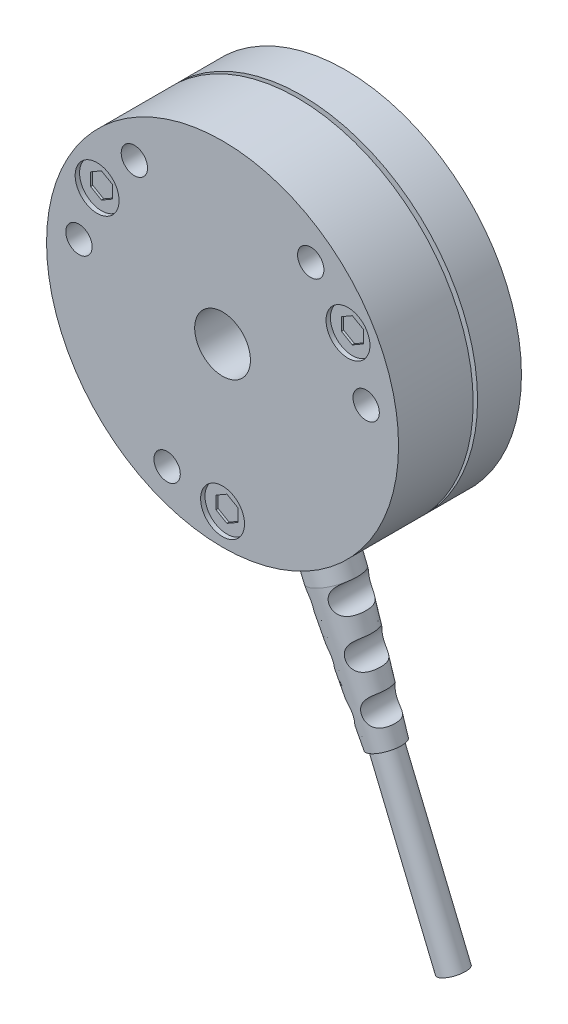
SolidWorks part; units mm, degrees
other "Camera1"
material "Plain Carbon Steel"
ref_plane "Front Plane" through (0, 0, 0) normal (0, 0, 1) x (1, 0, 0)
ref_plane "Top Plane" through (0, 0, 0) normal (0, 1, 0) x (1, 0, 0)
ref_plane "Right Plane" through (0, 0, 0) normal (1, 0, 0) x (0, 0, -1)
sketch "Sketch1" plane through (0, 0, 0) normal (0, 0, 1) x (1, 0, 0)
  circle A0 centre (0, 0) radius 20.05
  dimension "D1" = 40.1
extrude "Boss-Extrude1" add sketch "Sketch1" along normal blind 5
sketch "Sketch2" plane through (0, 0, 5) normal (0, 0, 1) x (1, 0, 0)
  circle A0 centre (0, 0) radius 18.5
  dimension "D1" = 37
extrude "Boss-Extrude2" add sketch "Sketch2" along normal blind 0.5
sketch "Sketch3" plane through (0, 0, 5.5) normal (0, 0, 1) x (1, 0, 0)
  circle A0 centre (0, 0) radius 20.05
extrude "Boss-Extrude3" add sketch "Sketch3" along normal blind 8.5
sketch "Sketch7" plane through (0, 0, 14) normal (0, 0, 1) x (1, 0, 0)
  line L0 (0, 0) -> (7.6728, -18.5238) construction
  line L1 (0, 20.05) -> (0, -20.05) construction
  line L2 (-18.5238, -7.6728) -> (18.5238, 7.6728)
  circle A0 centre (0, 0) radius 20.05 construction
  dimension "D1" = 22.5
sketch "Sketch8" plane through (0, 0, 0) normal (0, 0, -1) x (-1, 0, 0)
  line L0 (-18.5238, 7.6728) -> (18.5238, -7.6728)
ref_plane "Plane4" through (0, 0, 0) normal (-0.3827, 0.9239, 0) x (0.9239, 0.3827, 0)
sketch "Sketch4" plane through (0, 0, 0) normal (-0.3827, 0.9239, 0) x (0.9239, 0.3827, 0)
  line L0 (0, 0) -> (0, -14) construction
  line L1 (-20.05, -14) -> (20.05, -14) construction
  line L2 (-20.05, -7) -> (20.05, -7) construction
  line L3 (-20.05, -5.5) -> (-20.05, -14) construction
  line L4 (20.05, -14) -> (20.05, -5.5) construction
  circle A0 centre (0, -9.65) radius 2.65
  dimension "D1" = 5.3
  dimension "D2" = 7
extrude "Boss-Extrude4" add sketch "Sketch4" against normal blind 37.35 contours A0
chamfer "Chamfer1" distance 15 angle 3 1 edges at (11.8449, -35.521, 9.65) first distance on face at (11.8449, -35.521, 9.65)
sketch "Sketch5" plane through (14.2932, -34.5069, 0) normal (0.3827, -0.9239, 0) x (-0.9239, -0.3827, 0)
  circle A0 centre (0, -9.65) radius 1.5
  dimension "D1" = 3
extrude "Boss-Extrude5" add sketch "Sketch5" along normal blind 20
sketch "Sketch6" plane through (0, 0, 0) normal (0, 0, 1) x (1, 0, 0)
  line L0 (11.0013, -19.6346) -> (16.0152, -33.7936) construction
  line L1 (16.0152, -33.7936) -> (18.3361, -40.3477) construction
  line L2 (23.3327, -52.4105) -> (15.679, -33.9329) construction
  line L3 (6.1047, -21.6628) -> (12.5712, -35.2202) construction
  line L4 (12.5712, -35.2202) -> (15.5645, -41.4957) construction
  line L5 (12.9074, -35.0809) -> (20.5611, -53.5585) construction
  line L6 (-921.5262, -418.3454) -> (45272.4504, 18715.8262) construction
  line L7 (-922.1361, -413.1861) -> (45271.8405, 18720.9855) construction
  line L8 (6.1047, -21.6628) -> (11.0013, -19.6346) construction
  circle A0 centre (11.502, -21.0486) radius 1.5
  circle A1 centre (13.1733, -25.7682) radius 1.5
  circle A2 centre (14.8446, -30.4879) radius 1.5
  circle A3 centre (11.0615, -32.0549) radius 1.5
  circle A4 centre (8.906, -27.5358) radius 1.5
  circle A5 centre (6.7505, -23.0167) radius 1.5
  dimension "D1" = 3
  dimension "D2" = 5
  dimension "D3" = 5
extrude "Cut-Extrude1" cut sketch "Sketch6" along normal through all
sketch "Sketch9" plane through (0, 0, 14) normal (0, 0, 1) x (1, 0, 0)
  circle A0 centre (0, 0) radius 16.5 construction
  circle A1 centre (0, -16.5) radius 2.5
  circle A2 centre (-14.2894, 8.25) radius 2.5
  circle A3 centre (14.2894, 8.25) radius 2.5
  dimension "D1" = 33
  dimension "D2" = 5
  dimension "D3" = 3
extrude "Cut-Extrude2" cut sketch "Sketch9" against normal blind 0.5
sketch "Sketch10" plane through (0, 0, 13.5) normal (0, 0, 1) x (1, 0, 0)
  line L0 (-15.5394, 8.9717) -> (-15.5394, 7.5283)
  line L1 (0, -17.9434) -> (1.25, -17.2217)
  line L2 (1.25, -17.2217) -> (1.25, -15.7783)
  line L3 (1.25, -15.7783) -> (0, -15.0566)
  line L4 (0, -15.0566) -> (-1.25, -15.7783)
  line L5 (-1.25, -15.7783) -> (-1.25, -17.2217)
  line L6 (-1.25, -17.2217) -> (0, -17.9434)
  line L7 (-15.5394, 7.5283) -> (-14.2894, 6.8066)
  line L8 (-14.2894, 6.8066) -> (-13.0394, 7.5283)
  line L9 (-13.0394, 7.5283) -> (-13.0394, 8.9717)
  line L10 (-13.0394, 8.9717) -> (-14.2894, 9.6934)
  line L11 (-14.2894, 9.6934) -> (-15.5394, 8.9717)
  line L12 (15.5394, 8.9717) -> (14.2894, 9.6934)
  line L13 (14.2894, 9.6934) -> (13.0394, 8.9717)
  line L14 (13.0394, 8.9717) -> (13.0394, 7.5283)
  line L15 (13.0394, 7.5283) -> (14.2894, 6.8066)
  line L16 (14.2894, 6.8066) -> (15.5394, 7.5283)
  line L17 (15.5394, 7.5283) -> (15.5394, 8.9717)
  circle A0 centre (0, -16.5) radius 1.25 construction
  dimension "D1" = 2.5
  dimension "D2" = 3
extrude "Cut-Extrude3" cut sketch "Sketch10" against normal blind 0.25 contours L1 L2 L3 L4 L5 L6 | L0 L7 L8 L9 L10 L11 | L12 L13 L14 L15 L16 L17
sketch "Sketch11" plane through (0, 0, 14) normal (0, 0, 1) x (1, 0, 0)
  circle A0 centre (0, 0) radius 3.175
  dimension "D1" = 6.35
extrude "Cut-Extrude4" cut sketch "Sketch11" against normal through all contours A0
sketch "Sketch12" plane through (0, 0, 14) normal (0, 0, 1) x (1, 0, 0)
  line L0 (-18.5238, -7.6728) -> (18.5238, 7.6728) construction
  line L1 (0, 0) -> (-7.6728, -18.5238) construction
  line L2 (0, 20.05) -> (0, -20.05) construction
  circle A0 centre (0, 0) radius 16.5 construction
  circle A1 centre (0, 0) radius 20.05 construction
  circle A2 centre (-6.3143, -15.244) radius 1.5
  circle A3 centre (-10.0446, 13.0903) radius 1.5
  circle A4 centre (16.3588, 2.1537) radius 1.5
  point P9 (-6.3143, -15.244)
  dimension "D1" = 33
  dimension "D3" = 3
  dimension "D2" = 22.5
  dimension "D4" = 3
extrude "Cut-Extrude5" cut sketch "Sketch12" against normal blind 5
sketch "Sketch13" plane through (0, 0, 14) normal (0, 0, 1) x (1, 0, 0)
  line L0 (-20.05, 0) -> (20.05, 0) construction
  line L1 (0, 0) -> (-19.8785, 2.6171) construction
  line L2 (0, 0) -> (12.2057, 15.9067) construction
  circle A0 centre (0, 0) radius 20.05 construction
  arc A1 (10.0446, 13.0903) -> (-16.5, 0) centre (0, 0) ccw construction
  circle A2 centre (-16.3588, 2.1537) radius 1.5
  circle A3 centre (10.0446, 13.0903) radius 1.5
  point P11 (-16.3588, 2.1537)
  dimension "D3" = 16.5
  dimension "D4" = 3
  dimension "D5" = 3
  dimension "D1" = 7.5
  dimension "D2" = 120
extrude "Cut-Extrude6" cut sketch "Sketch13" against normal blind 5
sketch "Sketch14" plane through (0, 0, 0) normal (0, 0, -1) x (-1, 0, 0)
  line L0 (0, 0) -> (0, -16.5) construction
  circle A0 centre (0, 0) radius 16.5 construction
  circle A1 centre (0, -16.5) radius 1.5
  circle A2 centre (-14.2894, 8.25) radius 1.5
  circle A3 centre (14.2894, 8.25) radius 1.5
  dimension "D1" = 33
  dimension "D2" = 3
  dimension "D3" = 3
extrude "Cut-Extrude7" cut sketch "Sketch14" against normal blind 5
sketch "Sketch15" plane through (0, 0, 0) normal (0, 0, -1) x (-1, 0, 0)
  line L1 (0, 0) -> (-17.3638, -10.025) construction
  line L2 (18.5238, -7.6728) -> (-18.5238, 7.6728) construction
  line L3 (0, 0) -> (0, 20.05) construction
  circle A1 centre (0, 0) radius 20.05 construction
  circle A2 centre (0, 17.5) radius 1.5
  circle A3 centre (-15.1554, -8.75) radius 1.5
  dimension "D1" = 120
  dimension "D2" = 3
  dimension "D3" = 3
  dimension "D4" = 17.5
  dimension "D5" = 26.25
extrude "Cut-Extrude8" cut sketch "Sketch15" against normal blind 5
sketch "Sketch16" plane through (0, 0, 0) normal (0, 0, -1) x (-1, 0, 0)
  line L0 (0, 20.05) -> (0, -20.05) construction
  circle A0 centre (0, -7.5) radius 3.5
  circle A1 centre (-6.4952, 3.75) radius 3.5
  circle A2 centre (6.4952, 3.75) radius 3.5
  dimension "D1" = 7
  dimension "D2" = 7.5
  dimension "D3" = 3
extrude "Cut-Extrude9" cut sketch "Sketch16" against normal blind 0.5
sketch "Sketch17" plane through (0, 0, 0.5) normal (0, 0, -1) x (-1, 0, 0)
  line L0 (-7.7452, 4.4717) -> (-7.7452, 3.0283)
  line L1 (0, -8.9434) -> (1.25, -8.2217)
  line L2 (1.25, -8.2217) -> (1.25, -6.7783)
  line L3 (1.25, -6.7783) -> (0, -6.0566)
  line L4 (0, -6.0566) -> (-1.25, -6.7783)
  line L5 (-1.25, -6.7783) -> (-1.25, -8.2217)
  line L6 (-1.25, -8.2217) -> (0, -8.9434)
  line L7 (-7.7452, 3.0283) -> (-6.4952, 2.3066)
  line L8 (-6.4952, 2.3066) -> (-5.2452, 3.0283)
  line L9 (-5.2452, 3.0283) -> (-5.2452, 4.4717)
  line L10 (-5.2452, 4.4717) -> (-6.4952, 5.1934)
  line L11 (-6.4952, 5.1934) -> (-7.7452, 4.4717)
  line L12 (7.7452, 4.4717) -> (6.4952, 5.1934)
  line L13 (6.4952, 5.1934) -> (5.2452, 4.4717)
  line L14 (5.2452, 4.4717) -> (5.2452, 3.0283)
  line L15 (5.2452, 3.0283) -> (6.4952, 2.3066)
  line L16 (6.4952, 2.3066) -> (7.7452, 3.0283)
  line L17 (7.7452, 3.0283) -> (7.7452, 4.4717)
  circle A0 centre (0, -7.5) radius 1.25 construction
  dimension "D1" = 2.5
  dimension "D2" = 3
extrude "Cut-Extrude10" cut sketch "Sketch17" against normal blind 0.25 contours L1 L2 L3 L4 L5 L6 | L0 L7 L8 L9 L10 L11 | L12 L13 L14 L15 L16 L17
